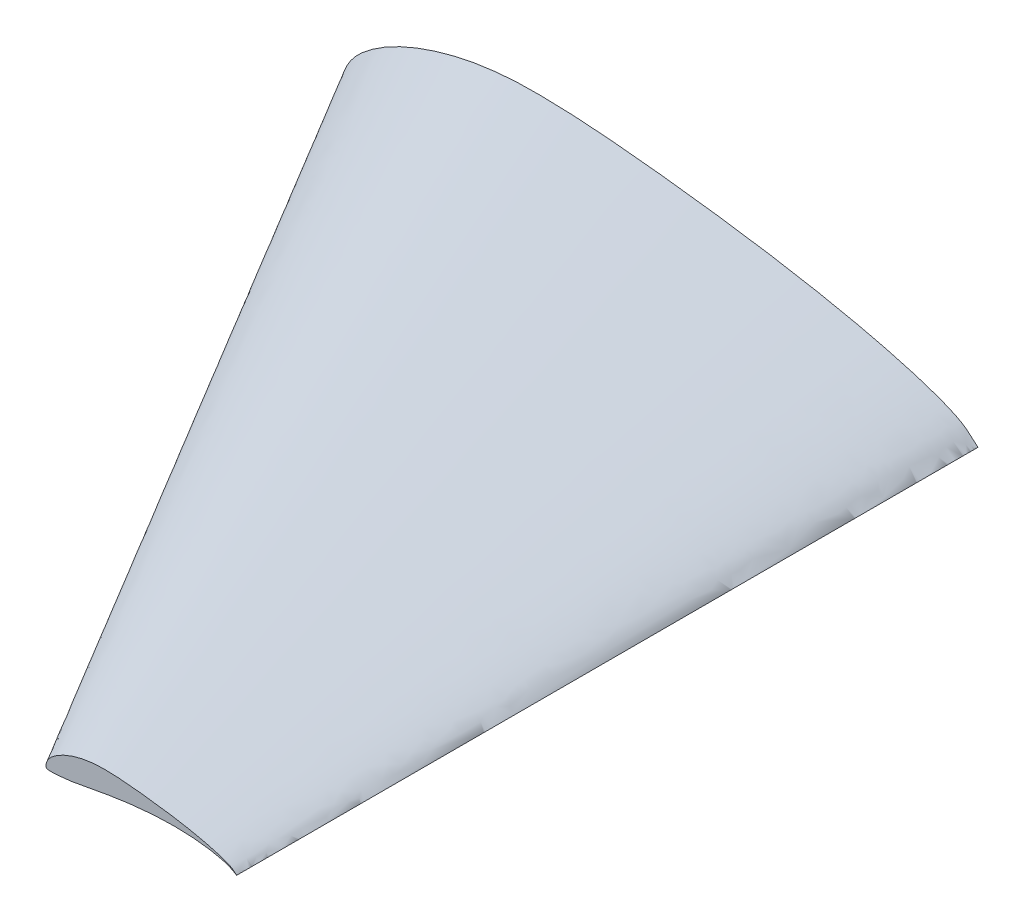
SolidWorks part; units mm, degrees
material "Nylon 101"
ref_plane "Front Plane" through (0, 0, 0) normal (0, 0, 1) x (1, 0, 0)
ref_plane "Top Plane" through (0, 0, 0) normal (0, 1, 0) x (1, 0, 0)
ref_plane "Right Plane" through (0, 0, 0) normal (1, 0, 0) x (0, 0, -1)
curve "Curve1"
  spline degree 3 poles (59.7678, 0.1558, 0) (60.0544, -0.0387, 0) (59.8031, 0.1485, 0) (59.6363, 0.3122, 0) (59.2659, 0.654, 0) (58.8289, 1.0177, 0) (58.2312, 1.3843, 0) (57.4879, 1.7396, 0) (56.5906, 2.1104, 0) (55.5406, 2.4917, 0) (54.3427, 2.8798, 0) (53.0045, 3.2753, 0) (51.5282, 3.6599, 0) (49.9319, 4.0656, 0) (48.2145, 4.4525, 0) (46.3922, 4.8372, 0) (44.4742, 5.2122, 0) (42.4721, 5.5744, 0) (40.3983, 5.9229, 0) (38.265, 6.2533, 0) (36.0858, 6.5663, 0) (33.8748, 6.8594, 0) (31.648, 7.1315, 0) (29.423, 7.3848, 0) (27.2185, 7.6127, 0) (25.0523, 7.811, 0) (22.9397, 7.9686, 0) (20.8927, 8.077, 0) (18.9227, 8.1238, 0) (17.0399, 8.1188, 0) (15.2476, 8.0266, 0) (13.5454, 7.8398, 0) (11.9261, 7.5756, 0) (10.3894, 7.2334, 0) (8.937, 6.8321, 0) (7.5748, 6.3788, 0) (6.3088, 5.8842, 0) (5.1469, 5.3508, 0) (4.0926, 4.7895, 0) (3.1518, 4.2068, 0) (2.3304, 3.6104, 0) (1.6286, 3.013, 0) (1.0568, 2.4081, 0) (0.6175, 1.801, 0) (0.293, 1.2104, 0) (0.0851, 0.6496, 0) (-0.014, 0.132, 0) (0.0051, -0.3058, 0) (0.1178, -0.7073, 0) (0.5368, -0.9066, 0) (1.1, -0.9346, 0) (1.8706, -0.9617, 0) (2.8397, -0.9199, 0) (3.9962, -0.8431, 0) (5.3274, -0.7201, 0) (6.8197, -0.5537, 0) (8.4657, -0.3402, 0) (10.2646, -0.0419, 0) (12.2253, 0.3321, 0) (14.3574, 0.7392, 0) (16.6507, 1.169, 0) (19.0906, 1.6038, 0) (21.6593, 2.0271, 0) (24.3369, 2.4248, 0) (27.1002, 2.7825, 0) (29.9244, 3.0895, 0) (32.7828, 3.3322, 0) (35.6468, 3.5043, 0) (38.4864, 3.5989, 0) (41.2709, 3.6108, 0) (43.9691, 3.5393, 0) (46.5501, 3.386, 0) (48.983, 3.153, 0) (51.2388, 2.849, 0) (53.288, 2.483, 0) (55.1067, 2.0673, 0) (56.6613, 1.6224, 0) (57.9337, 1.1476, 0) (58.8414, 0.7131, 0) (59.5107, 0.3113, 0) (59.7678, 0.1558, 0) (60.0544, -0.0387, 0) (59.8031, 0.1485, 0) knots -0.009748 -0.004147 -0.001 0 0.00098 0.003649 0.007484 0.012095 0.017526 0.024052 0.031783 0.040678 0.05071 0.061833 0.073978 0.087118 0.101144 0.11599 0.13157 0.147788 0.16455 0.181757 0.199311 0.217095 0.23499 0.252856 0.27054 0.287886 0.304773 0.321101 0.336806 0.3518 0.366031 0.379615 0.392653 0.40517 0.417171 0.428603 0.439419 0.449596 0.459102 0.467907 0.475988 0.483309 0.489874 0.495803 0.501149 0.505903 0.510046 0.513579 0.516447 0.51935 0.523823 0.529973 0.537715 0.546968 0.557637 0.56962 0.582804 0.597247 0.613135 0.630443 0.649056 0.668822 0.689595 0.711189 0.733426 0.756094 0.778988 0.80189 0.824566 0.846792 0.868338 0.888978 0.908492 0.926659 0.943286 0.958169 0.971136 0.981956 0.990252 0.995853 0.999 1 1.00098 1.003649 1.007484 periodic
sketch "Sketch2" plane through (0, 0, 0) normal (0, 0, 1) x (1, 0, 0)
  spline S0 degree 3 poles (59.7678, 0.1558) (60.0544, -0.0387) (59.8031, 0.1485) (59.6363, 0.3122) (59.2659, 0.654) (58.8289, 1.0177) (58.2312, 1.3843) (57.4879, 1.7396) (56.5906, 2.1104) (55.5406, 2.4917) (54.3427, 2.8798) (53.0045, 3.2753) (51.5282, 3.6599) (49.9319, 4.0656) (48.2145, 4.4525) (46.3922, 4.8372) (44.4742, 5.2122) (42.4721, 5.5744) (40.3983, 5.9229) (38.265, 6.2533) (36.0858, 6.5663) (33.8748, 6.8594) (31.648, 7.1315) (29.423, 7.3848) (27.2185, 7.6127) (25.0523, 7.811) (22.9397, 7.9686) (20.8927, 8.077) (18.9227, 8.1238) (17.0399, 8.1188) (15.2476, 8.0266) (13.5454, 7.8398) (11.9261, 7.5756) (10.3894, 7.2334) (8.937, 6.8321) (7.5748, 6.3788) (6.3088, 5.8842) (5.1469, 5.3508) (4.0926, 4.7895) (3.1518, 4.2068) (2.3304, 3.6104) (1.6286, 3.013) (1.0568, 2.4081) (0.6175, 1.801) (0.293, 1.2104) (0.0851, 0.6496) (-0.014, 0.132) (0.0051, -0.3058) (0.1178, -0.7073) (0.5368, -0.9066) (1.1, -0.9346) (1.8706, -0.9617) (2.8397, -0.9199) (3.9962, -0.8431) (5.3274, -0.7201) (6.8197, -0.5537) (8.4657, -0.3402) (10.2646, -0.0419) (12.2253, 0.3321) (14.3574, 0.7392) (16.6507, 1.169) (19.0906, 1.6038) (21.6593, 2.0271) (24.3369, 2.4248) (27.1002, 2.7825) (29.9244, 3.0895) (32.7828, 3.3322) (35.6468, 3.5043) (38.4864, 3.5989) (41.2709, 3.6108) (43.9691, 3.5393) (46.5501, 3.386) (48.983, 3.153) (51.2388, 2.849) (53.288, 2.483) (55.1067, 2.0673) (56.6613, 1.6224) (57.9337, 1.1476) (58.8414, 0.7131) (59.5107, 0.3113) (59.7678, 0.1558) (60.0544, -0.0387) (59.8031, 0.1485) knots -0.009748 -0.004147 -0.001 0 0.00098 0.003649 0.007484 0.012095 0.017526 0.024052 0.031783 0.040678 0.05071 0.061833 0.073978 0.087118 0.101144 0.11599 0.13157 0.147788 0.16455 0.181757 0.199311 0.217095 0.23499 0.252856 0.27054 0.287886 0.304773 0.321101 0.336806 0.3518 0.366031 0.379615 0.392653 0.40517 0.417171 0.428603 0.439419 0.449596 0.459102 0.467907 0.475988 0.483309 0.489874 0.495803 0.501149 0.505903 0.510046 0.513579 0.516447 0.51935 0.523823 0.529973 0.537715 0.546968 0.557637 0.56962 0.582804 0.597247 0.613135 0.630443 0.649056 0.668822 0.689595 0.711189 0.733426 0.756094 0.778988 0.80189 0.824566 0.846792 0.868338 0.888978 0.908492 0.926659 0.943286 0.958169 0.971136 0.981956 0.990252 0.995853 0.999 1 1.00098 1.003649 1.007484 only from (60, 0) to (60, 0) construction
  spline S1 degree 3 poles (59.7678, 0.1558) (60.0544, -0.0387) (59.8031, 0.1485) (59.6363, 0.3122) (59.2659, 0.654) (58.8289, 1.0177) (58.2312, 1.3843) (57.4879, 1.7396) (56.5906, 2.1104) (55.5406, 2.4917) (54.3427, 2.8798) (53.0045, 3.2753) (51.5282, 3.6599) (49.9319, 4.0656) (48.2145, 4.4525) (46.3922, 4.8372) (44.4742, 5.2122) (42.4721, 5.5744) (40.3983, 5.9229) (38.265, 6.2533) (36.0858, 6.5663) (33.8748, 6.8594) (31.648, 7.1315) (29.423, 7.3848) (27.2185, 7.6127) (25.0523, 7.811) (22.9397, 7.9686) (20.8927, 8.077) (18.9227, 8.1238) (17.0399, 8.1188) (15.2476, 8.0266) (13.5454, 7.8398) (11.9261, 7.5756) (10.3894, 7.2334) (8.937, 6.8321) (7.5748, 6.3788) (6.3088, 5.8842) (5.1469, 5.3508) (4.0926, 4.7895) (3.1518, 4.2068) (2.3304, 3.6104) (1.6286, 3.013) (1.0568, 2.4081) (0.6175, 1.801) (0.293, 1.2104) (0.0851, 0.6496) (-0.014, 0.132) (0.0051, -0.3058) (0.1178, -0.7073) (0.5368, -0.9066) (1.1, -0.9346) (1.8706, -0.9617) (2.8397, -0.9199) (3.9962, -0.8431) (5.3274, -0.7201) (6.8197, -0.5537) (8.4657, -0.3402) (10.2646, -0.0419) (12.2253, 0.3321) (14.3574, 0.7392) (16.6507, 1.169) (19.0906, 1.6038) (21.6593, 2.0271) (24.3369, 2.4248) (27.1002, 2.7825) (29.9244, 3.0895) (32.7828, 3.3322) (35.6468, 3.5043) (38.4864, 3.5989) (41.2709, 3.6108) (43.9691, 3.5393) (46.5501, 3.386) (48.983, 3.153) (51.2388, 2.849) (53.288, 2.483) (55.1067, 2.0673) (56.6613, 1.6224) (57.9337, 1.1476) (58.8414, 0.7131) (59.5107, 0.3113) (59.7678, 0.1558) (60.0544, -0.0387) (59.8031, 0.1485) knots -0.009748 -0.004147 -0.001 0 0.00098 0.003649 0.007484 0.012095 0.017526 0.024052 0.031783 0.040678 0.05071 0.061833 0.073978 0.087118 0.101144 0.11599 0.13157 0.147788 0.16455 0.181757 0.199311 0.217095 0.23499 0.252856 0.27054 0.287886 0.304773 0.321101 0.336806 0.3518 0.366031 0.379615 0.392653 0.40517 0.417171 0.428603 0.439419 0.449596 0.459102 0.467907 0.475988 0.483309 0.489874 0.495803 0.501149 0.505903 0.510046 0.513579 0.516447 0.51935 0.523823 0.529973 0.537715 0.546968 0.557637 0.56962 0.582804 0.597247 0.613135 0.630443 0.649056 0.668822 0.689595 0.711189 0.733426 0.756094 0.778988 0.80189 0.824566 0.846792 0.868338 0.888978 0.908492 0.926659 0.943286 0.958169 0.971136 0.981956 0.990252 0.995853 0.999 1 1.00098 1.003649 1.007484 only from (60, 0) to (60, 0)
ref_plane "Plane1" through (0, 0, 70) normal (0, 0, 1) x (1, 0, 0)
sketch "Sketch3" plane through (0, 0, 70) normal (0, 0, 1) x (1, 0, 0)
  spline S1 degree 3 poles (59.9303, 0.0467) (60.0163, -0.0116) (59.9409, 0.0445) (59.8909, 0.0936) (59.7798, 0.1962) (59.6487, 0.3053) (59.4694, 0.4153) (59.2464, 0.5219) (58.9772, 0.6331) (58.6622, 0.7475) (58.3028, 0.864) (57.9013, 0.9826) (57.4585, 1.098) (56.9796, 1.2197) (56.4644, 1.3358) (55.9177, 1.4512) (55.3423, 1.5636) (54.7416, 1.6723) (54.1195, 1.7769) (53.4795, 1.876) (52.8258, 1.9699) (52.1624, 2.0578) (51.4944, 2.1395) (50.8269, 2.2154) (50.1655, 2.2838) (49.5157, 2.3433) (48.8819, 2.3906) (48.2678, 2.4231) (47.6768, 2.4371) (47.112, 2.4356) (46.5743, 2.408) (46.0636, 2.3519) (45.5778, 2.2727) (45.1168, 2.17) (44.6811, 2.0496) (44.2724, 1.9136) (43.8927, 1.7653) (43.5441, 1.6052) (43.2278, 1.4369) (42.9455, 1.262) (42.6991, 1.0831) (42.4886, 0.9039) (42.317, 0.7224) (42.1852, 0.5403) (42.0879, 0.3631) (42.0255, 0.1949) (41.9958, 0.0396) (42.0015, -0.0917) (42.0353, -0.2122) (42.161, -0.272) (42.33, -0.2804) (42.5612, -0.2885) (42.8519, -0.276) (43.1989, -0.2529) (43.5982, -0.216) (44.0459, -0.1661) (44.5397, -0.1021) (45.0794, -0.0126) (45.6676, 0.0996) (46.3072, 0.2218) (46.9952, 0.3507) (47.7272, 0.4811) (48.4978, 0.6081) (49.3011, 0.7275) (50.13, 0.8347) (50.9773, 0.9269) (51.8348, 0.9997) (52.694, 1.0513) (53.5459, 1.0797) (54.3813, 1.0833) (55.1907, 1.0618) (55.965, 1.0158) (56.6949, 0.9459) (57.3716, 0.8547) (57.9864, 0.7449) (58.532, 0.6202) (58.9984, 0.4867) (59.3801, 0.3443) (59.6524, 0.2139) (59.8532, 0.0934) (59.9303, 0.0467) (60.0163, -0.0116) (59.9409, 0.0445) knots -0.009748 -0.004147 -0.001 0 0.00098 0.003649 0.007484 0.012095 0.017526 0.024052 0.031783 0.040678 0.05071 0.061833 0.073978 0.087118 0.101144 0.11599 0.13157 0.147788 0.16455 0.181757 0.199311 0.217095 0.23499 0.252856 0.27054 0.287886 0.304773 0.321101 0.336806 0.3518 0.366031 0.379615 0.392653 0.40517 0.417171 0.428603 0.439419 0.449596 0.459102 0.467907 0.475988 0.483309 0.489874 0.495803 0.501149 0.505903 0.510046 0.513579 0.516447 0.51935 0.523823 0.529973 0.537715 0.546968 0.557637 0.56962 0.582804 0.597247 0.613135 0.630443 0.649056 0.668822 0.689595 0.711189 0.733426 0.756094 0.778988 0.80189 0.824566 0.846792 0.868338 0.888978 0.908492 0.926659 0.943286 0.958169 0.971136 0.981956 0.990252 0.995853 0.999 1 1.00098 1.003649 1.007484 only from (60, 0) to (60, 0)
loft "Loft1" add profiles "Sketch3", "Sketch2" connector at (60, 0, 70) connector at (60, 0, 0)
sketch "Sketch4" plane through (0, 0, 0) normal (0, 0, -1) x (-1, 0, 0)
  line L0 (-40.02, 5) -> (-7, 5) construction
  line L1 (-40.02, 5) -> (-27.02, 5) construction
  line L2 (-40.02, 5.75) -> (-27.02, 5.75)
  line L3 (-40.02, 4.25) -> (-27.02, 4.25)
  line L4 (-23.51, 17.017) -> (-23.51, -6.1995) construction
  line L5 (-7, 5) -> (-20, 5) construction
  line L6 (-7, 5.75) -> (-20, 5.75)
  line L7 (-7, 4.25) -> (-20, 4.25)
  circle A0 centre (-23.51, 5) radius 2
  arc A1 (-40.02, 5.75) -> (-40.02, 4.25) centre (-40.02, 5) ccw
  arc A2 (-27.02, 4.25) -> (-27.02, 5.75) centre (-27.02, 5) ccw
  arc A3 (-7, 5.75) -> (-7, 4.25) centre (-7, 5) cw
  arc A4 (-20, 4.25) -> (-20, 5.75) centre (-20, 5) cw
  point P6 (-33.52, 5)
  point P14 (-13.5, 5)
  dimension "D4" = 4
  dimension "D5" = 0.75
  dimension "D1" = 33.02
  dimension "D2" = 7
  dimension "D3" = 5
  dimension "D6" = 13
extrude "Cut-Extrude1" cut sketch "Sketch4" against normal blind 10 contours A0 region at (23.51, 5, 0)
extrude "Cut-Extrude2" cut sketch "Sketch4<3>" against normal blind 1 contours L2 A2 L3 A1 | L7 A4 L6 A3
sketch "Sketch4<3>" plane through (0, 0, 0) normal (0, 0, -1) x (-1, 0, 0) same geometry as "Sketch4"
